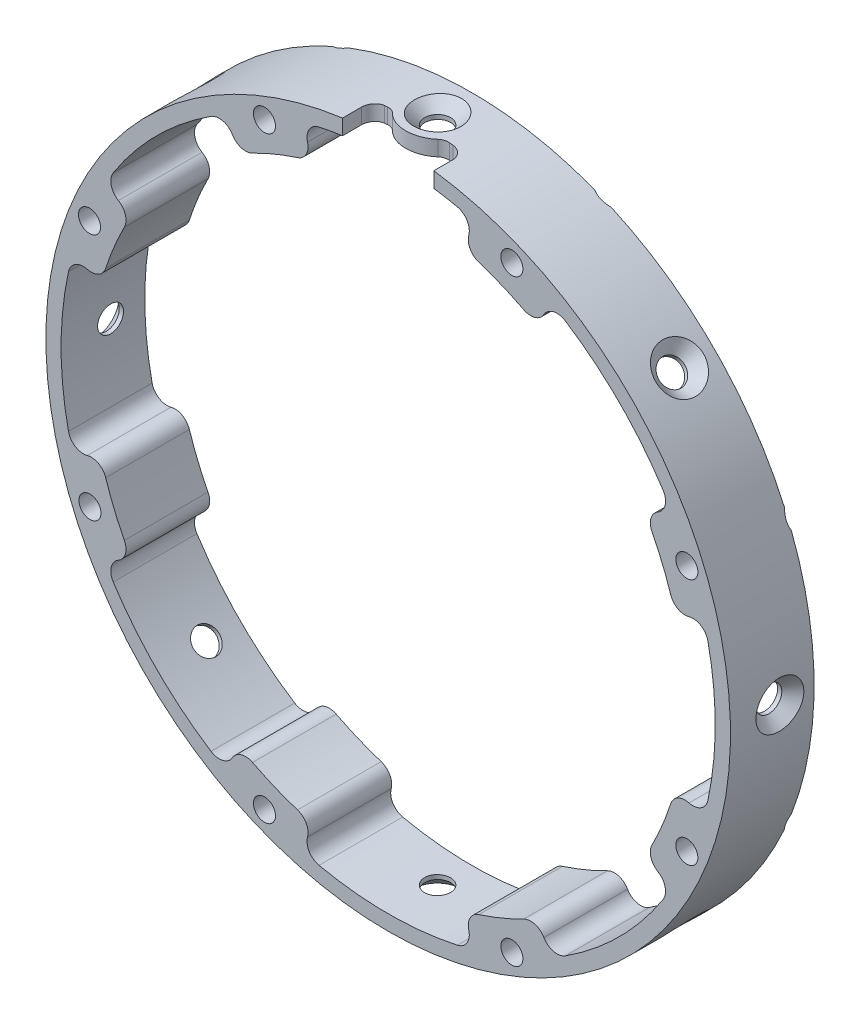
SolidWorks part; units mm, degrees
ref_plane "前视基准面" through (0, 0, 0) normal (0, 0, 1) x (1, 0, 0)
ref_plane "上视基准面" through (0, 0, 0) normal (0, 1, 0) x (1, 0, 0)
ref_plane "右视基准面" through (0, 0, 0) normal (1, 0, 0) x (0, 0, -1)
sketch "草图1" plane through (0, 0, 0) normal (0, 0, 1) x (1, 0, 0)
  line L0 (11.1292, 41.5348) -> (10.0939, 37.6711)
  line L17 (21.5, 37.2391) -> (19.5, 33.775)
  line L18 (-11.1292, 41.5348) -> (-10.0939, 37.6711)
  line L19 (37.2391, 21.5) -> (33.775, 19.5)
  line L20 (41.5348, 11.1292) -> (37.6711, 10.0939)
  line L21 (41.5348, -11.1292) -> (37.6711, -10.0939)
  line L22 (37.2391, -21.5) -> (33.775, -19.5)
  line L23 (21.5, -37.2391) -> (19.5, -33.775)
  line L24 (11.1292, -41.5348) -> (10.0939, -37.6711)
  line L25 (-11.1292, -41.5348) -> (-10.0939, -37.6711)
  line L26 (-21.5, -37.2391) -> (-19.5, -33.775)
  line L27 (-37.2391, -21.5) -> (-33.775, -19.5)
  line L28 (-41.5348, -11.1292) -> (-37.6711, -10.0939)
  line L29 (-41.5348, 11.1292) -> (-37.6711, 10.0939)
  line L30 (-37.2391, 21.5) -> (-33.775, 19.5)
  line L31 (-21.5, 37.2391) -> (-19.5, 33.775)
  circle A1 centre (0, 0) radius 45
  arc A3 (10.0939, 37.6711) -> (19.5, 33.775) centre (0, 0) cw
  arc A4 (11.1292, 41.5348) -> (-11.1292, 41.5348) centre (0, 0) ccw
  arc A21 (37.2391, 21.5) -> (21.5, 37.2391) centre (0, 0) ccw
  arc A22 (33.775, 19.5) -> (37.6711, 10.0939) centre (0, 0) cw
  arc A23 (41.5348, -11.1292) -> (41.5348, 11.1292) centre (0, 0) ccw
  arc A24 (37.6711, -10.0939) -> (33.775, -19.5) centre (0, 0) cw
  arc A25 (21.5, -37.2391) -> (37.2391, -21.5) centre (0, 0) ccw
  arc A26 (19.5, -33.775) -> (10.0939, -37.6711) centre (0, 0) cw
  arc A27 (-11.1292, -41.5348) -> (11.1292, -41.5348) centre (0, 0) ccw
  arc A28 (-10.0939, -37.6711) -> (-19.5, -33.775) centre (0, 0) cw
  arc A29 (-37.2391, -21.5) -> (-21.5, -37.2391) centre (0, 0) ccw
  arc A30 (-33.775, -19.5) -> (-37.6711, -10.0939) centre (0, 0) cw
  arc A31 (-41.5348, 11.1292) -> (-41.5348, -11.1292) centre (0, 0) ccw
  arc A32 (-37.6711, 10.0939) -> (-33.775, 19.5) centre (0, 0) cw
  arc A33 (-21.5, 37.2391) -> (-37.2391, 21.5) centre (0, 0) ccw
  arc A34 (-19.5, 33.775) -> (-10.0939, 37.6711) centre (0, 0) cw
  point P51 (0, 0)
  point P56 (0, 0)
  dimension "D1" = 8
extrude "凸台-拉伸1" add sketch "草图1" against normal blind 11
hole_wizard "M3 锥坑平头的锥孔2" positions "3D草图3" profile "草图4" countersink size "M3" standard "BSI" end condition through all
sketch3d "3D草图3"
  point P67 (31.8198, 31.8198, -6.5)
  point P76 (45, 0, -6.5)
  point P83 (31.8198, -31.8198, -6.5)
  point P85 (-31.8198, 31.8198, -6.5)
  point P87 (-31.8198, -31.8198, -6.5)
  point P96 (0, -45, -6.5)
  point P98 (0, 45, -6.5)
  point P105 (-45, 0, -6.5)
sketch "草图4" plane through (31.8198, 31.8198, -6.5) normal (0, 0, 1) x (-0.7071, 0.7071, 0)
  line L0 (0, 0) -> (0, 108.6396)
  line L1 (0, 108.6396) -> (1.7, 108.6396)
  line L2 (1.7, 108.6396) -> (1.7, 1.45)
  line L3 (1.7, 1.45) -> (3.15, 0)
  line L5 (3.15, 0) -> (0, 0)
  line L6 (-1.7, 1.45) -> (-3.15, 0) construction
  line L11 (0, -6.35) -> (0, 107.95) construction
  dimension "通孔孔直径" = 3.4
  dimension "通孔孔深度" = 108.6396
  dimension "近端锥形沉头孔直径" = 6.3
  dimension "近端锥形沉头孔角度" = 90
ref_plane "基准面1" through (0, 45, 0) normal (0, 1, 0) x (1, 0, 0)
sketch "草图7" plane through (0, 45, 0) normal (0, 1, 0) x (1, 0, 0)
  line L0 (-6, 0) -> (6, 0)
  line L1 (-45, 0) -> (45, 0) construction
  line L2 (6, 0) -> (6, 4)
  line L3 (6, 4) -> (3.3749, 4)
  line L5 (-6, 0) -> (-6, 4)
  line L6 (-6, 4) -> (-3.3749, 4)
  arc A1 (3.3749, 4) -> (-3.3749, 4) centre (0, 6.5) cw
extrude "切除-拉伸1" cut sketch "草图7" against normal up to next
hole_wizard "M2.5 锥坑平头的锥孔2" positions "3D草图4" profile "草图8" countersink size "M2.5" standard "BSI" end condition up to next
sketch3d "3D草图4"
  point P13 (39.2649, 16.264, -11)
  point P19 (16.264, 39.2649, -11)
  point P21 (-16.264, 39.2649, -11)
  point P23 (39.2649, -16.264, -11)
  point P26 (-39.2649, 16.264, -11)
  point P28 (-39.2044, -16.264, -11)
  point P30 (-16.264, -39.2649, -11)
  point P32 (16.264, -39.2649, -11)
sketch "草图8" plane through (39.2649, 16.264, -11) normal (1, 0, 0) x (0, 1, 0)
  line L0 (0, 0) -> (0, 11)
  line L1 (0, 11) -> (1.45, 11)
  line L2 (1.45, 11) -> (1.45, 1.3)
  line L3 (1.45, 1.3) -> (2.75, 0)
  line L5 (2.75, 0) -> (0, 0)
  line L6 (-1.45, 1.3) -> (-2.75, 0) construction
  line L11 (0, -6.35) -> (0, 107.95) construction
  dimension "通孔孔直径" = 2.9
  dimension "通孔孔深度" = 11
  dimension "近端锥形沉头孔直径" = 5.5
  dimension "近端锥形沉头孔角度" = 90
fillet "圆角1" radius 2 32 edges at (-41.5348, -11.1292, -5.5) (-37.6711, -10.0939, -5.5) (-33.775, -19.5, -5.5) (-37.2391, -21.5, -5.5) (-21.5, -37.2391, -5.5) (-10.0939, -37.6711, -5.5) (-19.5, -33.775, -5.5) (-11.1292, -41.5348, -5.5) (11.1292, -41.5348, -5.5) (10.0939, -37.6711, -5.5) (19.5, -33.775, -5.5) (21.5, -37.2391, -5.5) (37.2391, -21.5, -5.5) (33.775, -19.5, -5.5) (37.6711, -10.0939, -5.5) (41.5348, -11.1292, -5.5) (41.5348, 11.1292, -5.5) (37.6711, 10.0939, -5.5) (33.775, 19.5, -5.5) (37.2391, 21.5, -5.5) (21.5, 37.2391, -5.5) (11.1292, 41.5348, -5.5) (10.0939, 37.6711, -5.5) (19.5, 33.775, -5.5) (-11.1292, 41.5348, -5.5) (-10.0939, 37.6711, -5.5) (-21.5, 37.2391, -5.5) (-19.5, 33.775, -5.5) (-37.2391, 21.5, -5.5) (-33.775, 19.5, -5.5) (-37.6711, 10.0939, -5.5) (-41.5348, 11.1292, -5.5)
fillet "圆角2" radius 1.5 4 edges at (-6, 43.5888, -4) (6, 43.5888, -4) (-3.3749, 43.8703, -4) (3.3749, 43.8703, -4)
